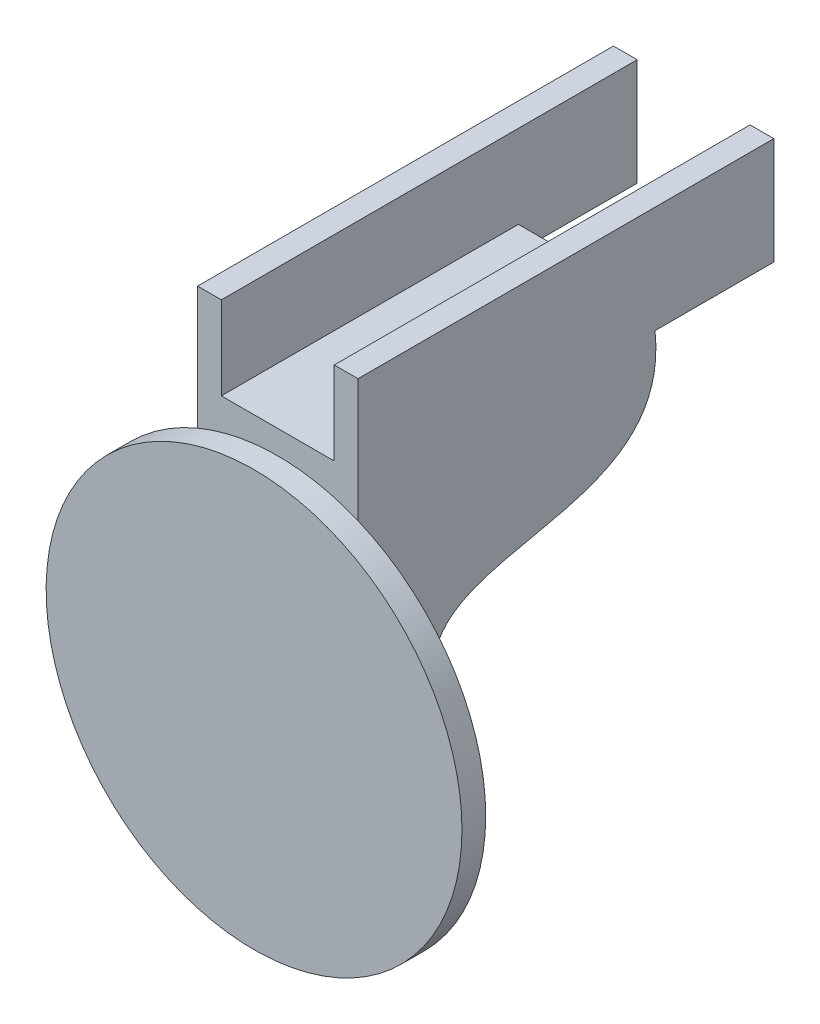
SolidWorks part; units mm, degrees
ref_plane "Alzado" through (0, 0, 0) normal (0, 0, 1) x (1, 0, 0)
ref_plane "Planta" through (0, 0, 0) normal (0, 1, 0) x (1, 0, 0)
ref_plane "Vista lateral" through (0, 0, 0) normal (1, 0, 0) x (0, 0, -1)
sketch "Croquis3" plane through (0, 0, 0) normal (0, 0, 1) x (1, 0, 0)
  line L0 (-207.1321, -11.9301) -> (-207.1321, -18.9301)
  line L1 (-207.1321, -11.9301) -> (-205.1321, -11.9301)
  line L2 (-205.1321, -11.9301) -> (-205.1321, -18.9301)
  line L3 (-205.1321, -18.9301) -> (-195.6321, -18.9301)
  line L4 (-195.6321, -18.9301) -> (-195.6321, -11.9301)
  line L5 (-195.6321, -11.9301) -> (-193.6321, -11.9301)
  line L6 (-193.6321, -11.9301) -> (-193.6321, -20.9301)
  line L7 (-193.6321, -20.9301) -> (-207.1321, -20.9301)
  line L8 (-207.1321, -20.9301) -> (-207.1321, -18.9301)
  dimension "D1" = 7
  dimension "D2" = 9
  dimension "D3" = 2
  dimension "D4" = 2
  dimension "D5" = 13.5
extrude "Saliente-Extruir2" add sketch "Croquis3" along normal blind 35
sketch "Croquis4" plane through (0, -18.9301, 0) normal (0, 1, 0) x (1, 0, 0)
  line L0 (-195.6321, -35) -> (-195.6321, 0) construction
  line L1 (-205.1321, 0) -> (-195.6321, 0)
  line L2 (-205.1321, 0) -> (-205.1321, -10)
  line L3 (-205.1321, -10) -> (-195.6321, -10)
  line L4 (-195.6321, 0) -> (-195.6321, -10)
  dimension "D1" = 10
extrude "Cortar-Extruir1" cut sketch "Croquis4" against normal blind 70
sketch "Croquis5" plane through (-193.6321, 0, 0) normal (1, 0, 0) x (0, 0, -1)
  line L0 (-35, -20.9301) -> (-35, -55.9301)
  line L1 (-35, -20.9301) -> (-10, -20.9301)
  line L2 (-35, -20.9301) -> (0, -20.9301) construction
  spline S0 degree 3 poles (-10, -20.9301) (-8.7547, -32.6228) (-40.4363, -25.169) (-23.0609, -54.2873) (-35, -55.9301) knots 0 0 0 0 0.470804 1 1 1 1
  dimension "D1" = 35
  dimension "D2" = 25
extrude "Saliente-Extruir3" add sketch "Croquis5" against normal up to vertex (13.5 mm away) up to point (-207.1321, -20.9301, 0)
sketch "Croquis7" plane through (0, 0, 35) normal (0, 0, 1) x (1, 0, 0)
  line L0 (-200.3821, -55.9301) -> (-200.3821, -38.4301) construction
  line L1 (-207.1321, -55.9301) -> (-193.6321, -55.9301) construction
  circle A0 centre (-200.3821, -38.4301) radius 17.5
  dimension "D1" = 17.5
extrude "Saliente-Extruir4" add sketch "Croquis7" along normal blind 2
sketch "Croquis8" plane through (0, 0, 35) normal (0, 0, 1) x (1, 0, 0)
  line L0 (-193.6321, -54.576) -> (-193.6321, -55.9301)
  line L1 (-193.6321, -55.9301) -> (-207.1321, -55.9301)
  line L2 (-200.3821, -55.9301) -> (-200.3821, -53.7897) construction
  line L3 (-207.1321, -54.576) -> (-207.1321, -55.9301)
  arc A0 (-193.6321, -54.576) -> (-207.1321, -54.576) centre (-200.3821, -38.4301) cw
  arc M1 (-193.6321, -54.576) -> (-200.3821, -55.9301) centre (-200.3821, -38.4301) cw
  line M2 (-200.3821, -55.9301) -> (-193.6321, -55.9301)
  line M3 (-193.6321, -55.9301) -> (-193.6321, -54.576)
extrude "Cortar-Extruir2" cut sketch "Croquis8" against normal blind 5 contours M3 M1 M2 | L1 A0 L3 region at (-205.458, -55.5267, 35) region at (-195.3063, -55.5267, 35)
